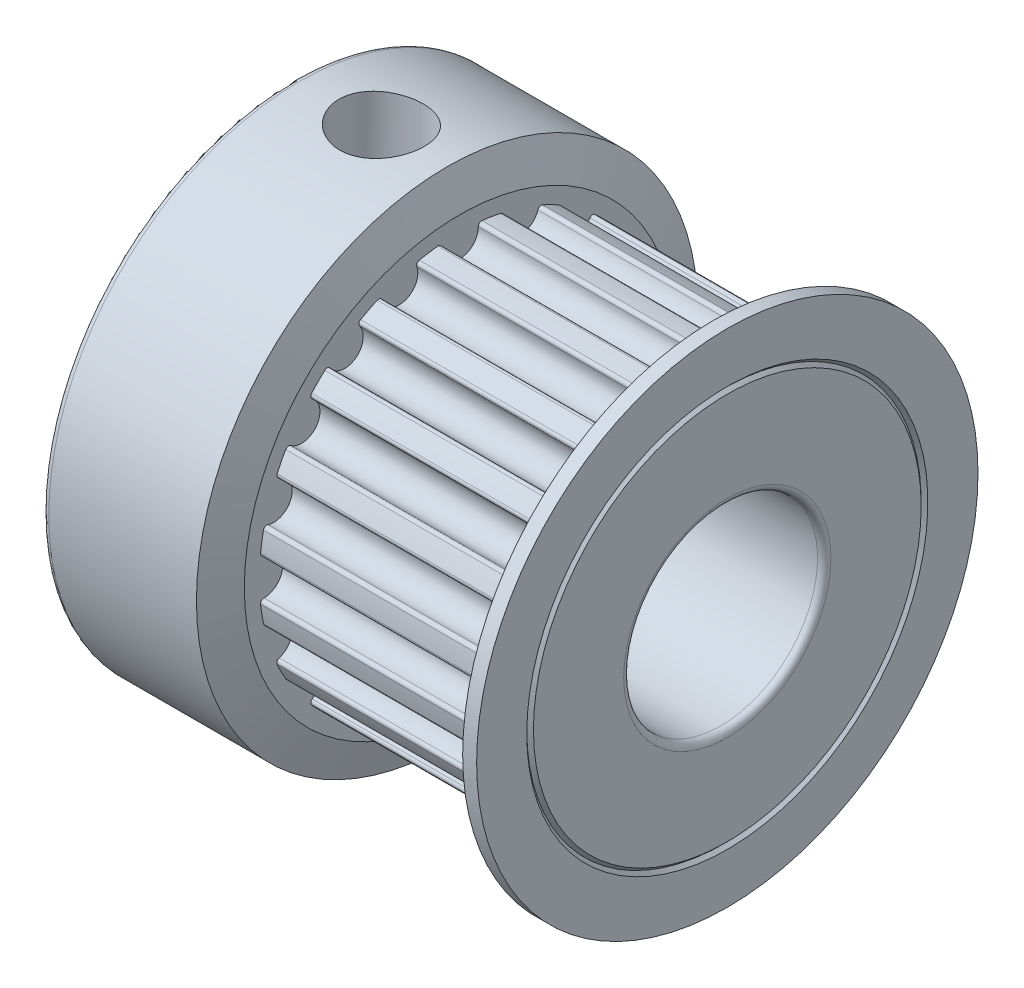
SolidWorks part; units mm, degrees
material "1.2311 (40CrMnMo7)"
ref_plane "Front" through (0, 0, 0) normal (0, 0, 1) x (1, 0, 0)
ref_plane "Top" through (0, 0, 0) normal (0, 1, 0) x (1, 0, 0)
ref_plane "Right" through (0, 0, 0) normal (1, 0, 0) x (0, 0, -1)
sketch "Sketch 1" plane through (0, 0, 0) normal (0, 0, 1) x (1, 0, 0)
  line L0 (1, 2.9) -> (1, 7.5)
  line L1 (1, 0) -> (14, 0) construction
  line L2 (1, 7.5) -> (5.6176, 7.5)
  line L3 (5.6176, 7.5) -> (6, 6.4494)
  line L4 (6, 6) -> (13.2, 6)
  line L5 (13.2, 6) -> (13.2, 6.4494)
  line L6 (13.5824, 7.5) -> (14, 7.5)
  line L7 (14, 2.9) -> (14, 5.8)
  line L8 (14, 5.8) -> (13.9, 5.9)
  line L9 (13.9, 5.9) -> (14, 6)
  line L10 (14, 6) -> (14, 7.5)
  line L11 (14, 2.9) -> (1, 2.9)
  line L12 (6, 6.4494) -> (6, 6)
  line L13 (13.2, 6.4494) -> (13.5824, 7.5)
  dimension "D1" = 5
  dimension "D2" = 20
  dimension "D5" = 0.1
  dimension "D8" = 7.2
revolve "Body" add sketch "Sketch 1" angle 360 about L1 region at (7.0145, 4.8392, 0)
sketch "Sketch 3" plane through (6, 0, 0) normal (1, 0, 0) x (0, 0, -1)
  line L0 (0, 0) -> (9.7637, 0) construction
  circle A18 centre (0, 5.855) radius 0.55
  point P45 (0, 0)
extrude "Cut-Extrude1" cut sketch "Sketch 3" along normal up to surface (7.2 mm away) up to face at (13.2, 0, 6.4494)
fillet "Fillet" radius 0.1 2 edges at (9.6, 5.976, -0.5365) (9.6, 5.976, 0.5365)
ref_axis "Axis1" through (0.35, 0, 0) along (1, 0, 0)
pattern_circular "CirPattern1" count 20 over 360 about axis through (0.35, 0, 0) along (1, 0, 0) of "Cut-Extrude1", "Fillet"
hole_wizard "M3 Tapped Hole1" positions "3DSketch1" profile "Sketch1" tap size "M3" standard "DIN"
sketch3d "3DSketch1"
  point P0 (3.5, 7.4984, -0.1544)
  dimension "D1" = 2.5
sketch "Sketch1" plane through (3.5, 7.4984, -0.1544) normal (1, 0, 0) x (0, 0.0206, 0.9998)
  line L0 (0, 0) -> (0, 8.2511)
  line L1 (0, 8.2511) -> (1.25, 7.5)
  line L2 (1.25, 7.5) -> (1.25, 0)
  line L5 (1.25, 0) -> (0, 0)
  line L10 (0, 8.2511) -> (-1.25, 7.5) construction
  line L11 (0, -6.35) -> (0, 107.95) construction
  dimension "Tap Drill Dia." = 2.5
  dimension "Tap Drill Depth" = 7.5
  dimension "Drill Angle" = 118
cosmetic thread "Hole Thread1" parameters "D1"=4.8832, "D2"=3
fillet "Fillet1" radius 0.2 4 edges at (14, 0, 2.9) (1, 0, 2.9) (3.6689, 2.5962, -1.2922) (1, 0, 7.5)
